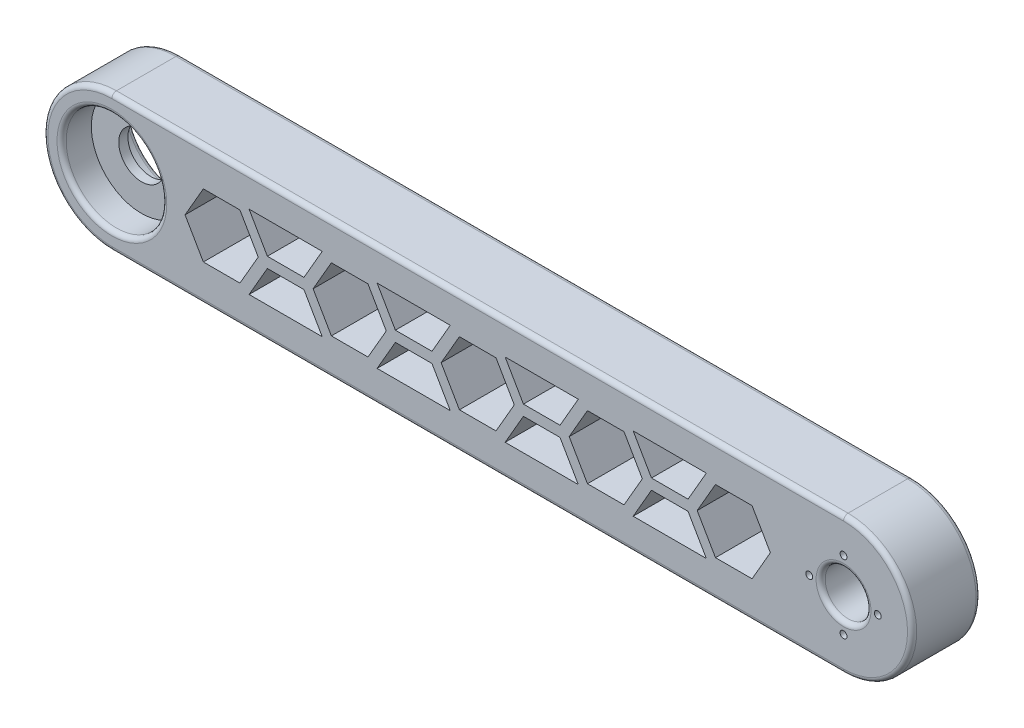
SolidWorks part; units mm, degrees
ref_plane "Front Plane" through (0, 0, 0) normal (0, 0, 1) x (1, 0, 0)
ref_plane "Top Plane" through (0, 0, 0) normal (0, 1, 0) x (1, 0, 0)
ref_plane "Right Plane" through (0, 0, 0) normal (1, 0, 0) x (0, 0, -1)
ref_axis "X" through (-88.99, 0, 0) along (1, 0, 0)
ref_axis "Y" through (0, 55, 0) along (0, -1, 0)
ref_axis "Z" through (0, 0, -88.99) along (0, 0, 1)
sketch "Sketch1" plane through (0, 0, 0) normal (0, 0, 1) x (1, 0, 0)
  line L0 (-80, 0) -> (80, 0) construction
  line L2 (-80, 15) -> (80, 15)
  line L3 (-80, -15) -> (80, -15)
  arc A0 (-80, 15) -> (-80, -15) centre (-80, 0) ccw
  arc A1 (80, -15) -> (80, 15) centre (80, 0) ccw
  circle A2 centre (80, 0) radius 11
  circle A3 centre (-80, 0) radius 11
  circle A4 centre (-80, 0) radius 5
  circle A5 centre (80, 0) radius 5
  point P5 (0, 0)
  dimension "D2" = 15
  dimension "D3" = 22
  dimension "D4" = 10
  dimension "D1" = 160
extrude "Boss-Extrude1" add sketch "Sketch1" along normal mid plane 2 contours L3 A1 L2 A0 A3 A2 | A4 A3 | A2 A5 region at (0, 0, 0) region at (69.3111, 0, 0) region at (-90.6889, 0, 0)
extrude "Boss-Extrude2" add sketch "Sketch1<3>" along normal mid plane 15 contours L3 A1 L2 A0 A3 A2 region at (0, 0, 0)
sketch "Sketch1<3>" plane through (0, 0, 0) normal (0, 0, 1) x (1, 0, 0) same geometry as "Sketch1"
sketch "Sketch2" plane through (0, 0, 0) normal (1, 0, 0) x (0, 0, -1)
  line L0 (-7.5, 15) -> (7.5, 15) construction
  line L1 (-7.5, 15) -> (7.5, 15)
  arc A0 (-3, 15) -> (3, 15) centre (0, 15) ccw
  point P6 (0, 15)
  dimension "D1" = 3
extrude "Cut-Extrude1" [suppressed] cut sketch "Sketch2" against normal through all both and the other way through all contours L1 A0
fillet "Fillet1" [suppressed] radius 1
mirror "Mirror3" [suppressed] about plane through (0, 0, 0) normal (0, 1, 0)
sketch "Sketch3" plane through (0, 0, 1) normal (0, 0, 1) x (1, 0, 0)
  circle A1 centre (80, 0) radius 11
  circle A2 centre (80, 0) radius 11
  circle A3 centre (80, 0) radius 5 construction
  circle A4 centre (80, 0) radius 5
  dimension "D1" = 0
extrude "Boss-Extrude3" add sketch "Sketch3" along normal up to surface (6.5 mm away) up to face at (91, 0, 7.5)
fillet "Fillet2" radius 1 12 edges at (-95, 0, 7.5) (0, 15, 7.5) (95, 0, 7.5) (0, -15, 7.5) (-69, 0, 7.5) (85, 0, 7.5) (95, 0, -7.5) (0, 15, -7.5) (-95, 0, -7.5) (0, -15, -7.5) (-69, 0, -7.5) (91, 0, -7.5)
mirror "Mirror1" [suppressed] about plane through (0, 0, 0) normal (1, 0, 0) of bodies 104
delete or keep bodies "Body-Delete/Keep 1" [suppressed] type keep bodies bodies 105
sketch "Sketch4" plane through (0, 0, 7.5) normal (0, 0, 1) x (1, 0, 0)
  circle A18 centre (87.5, 0) radius 0.75 construction
  circle A19 centre (80, -7.5) radius 0.75 construction
  circle A20 centre (72.5, 0) radius 0.75 construction
  circle A21 centre (80, 7.5) radius 0.75 construction
  circle A22 centre (87.5, 0) radius 0.75
  circle A23 centre (80, -7.5) radius 0.75
  circle A24 centre (72.5, 0) radius 0.75
  circle A25 centre (80, 7.5) radius 0.75
extrude "Cut-Extrude2" cut sketch "Sketch4" against normal offset from surface (6.5 mm away) 2 up to face at (85, 0, -1)
sketch "Sketch5" plane through (0, 0, 0) normal (0, 0, 1) x (1, 0, 0)
  line L0 (6, 8.0829) -> (10, 1.1547)
  line L1 (4, -6.9282) -> (8, 0)
  line L2 (8, 0) -> (4, 6.9282)
  line L3 (4, 6.9282) -> (-4, 6.9282)
  line L4 (-4, 6.9282) -> (-8, 0)
  line L5 (-8, 0) -> (-4, -6.9282)
  line L6 (-4, -6.9282) -> (4, -6.9282)
  line L7 (10, 1.1547) -> (18, 1.1547)
  line L8 (18, 1.1547) -> (22, 8.0829)
  line L9 (22, 8.0829) -> (6, 8.0829)
  line L10 (6, 3.4641) -> (8, 4.6188) construction
  line L11 (0, 0) -> (8, 0) construction
  line L12 (10, -1.1547) -> (18, -1.1547)
  line L13 (18, -1.1547) -> (22, -8.0829)
  line L14 (22, -8.0829) -> (6, -8.0829)
  line L15 (6, -8.0829) -> (10, -1.1547)
  circle A0 centre (0, 0) radius 6.9282 construction
  dimension "D1" = 8
  dimension "D2" = 2
extrude "Cut-Extrude3" cut sketch "Sketch5" against normal through all both and the other way through all contours L5 L6 L1 L2 L3 L4 region at (0, 0, 0)
extrude "Cut-Extrude4" cut sketch "Sketch5<3>" against normal through all both and the other way through all contours L15 L14 L13 L12 | L8 L9 L0 L7 region at (14, 5.0037, 0) region at (14, -5.0037, 0)
sketch "Sketch5<3>" plane through (0, 0, 0) normal (0, 0, 1) x (1, 0, 0) same geometry as "Sketch5"
pattern_linear "LPattern1" count 3 spacing 28 along (1, 0, 0) count 3 spacing 28 along (-1, 0, 0) of "Cut-Extrude3"
pattern_linear "LPattern2" count 2 spacing 28 along (1, 0, 0) count 3 spacing 28 along (-1, 0, 0) of "Cut-Extrude4"
